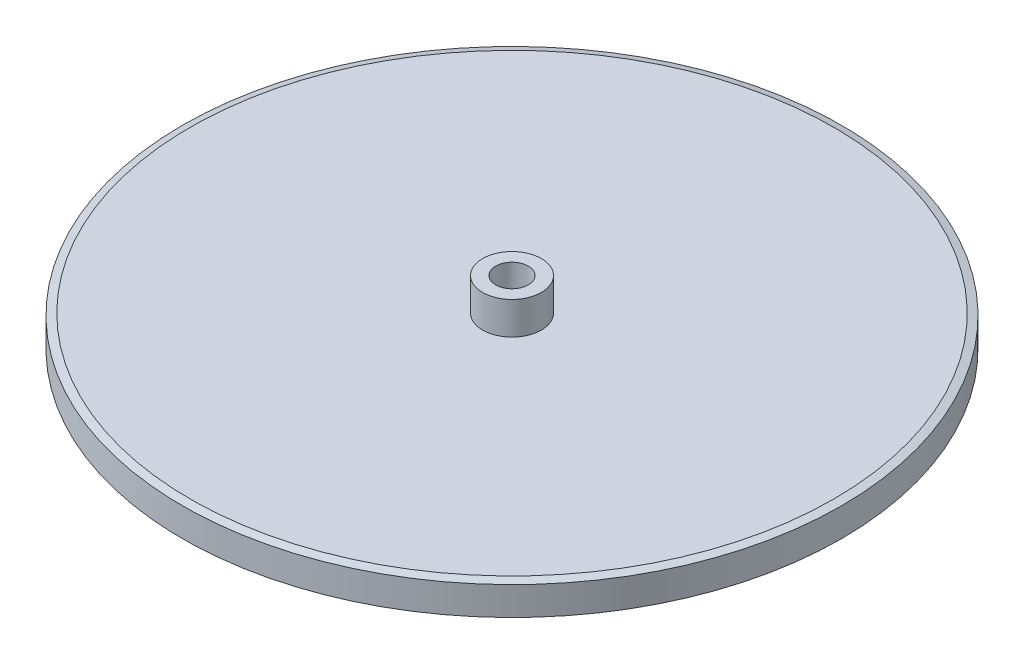
SolidWorks part; units mm, degrees
material "Сталь ШХ15 ГОСТ 801-78"
ref_plane "Plane1" through (0, 0, 0) normal (0, 0, 1) x (1, 0, 0)
ref_plane "Plane2" through (0, 0, 0) normal (0, 1, 0) x (1, 0, 0)
ref_plane "Plane3" through (0, 0, 0) normal (1, 0, 0) x (0, 0, -1)
sketch "Эскиз1" plane through (0, 0, 0) normal (0, 0, 1) x (1, 0, 0)
  line L0 (0, 0) -> (50.5, 0)
  line L1 (50.5, 0) -> (50.5, 5)
  line L2 (50.5, 5) -> (4.5, 5)
  line L3 (4.5, 5) -> (4.5, 10)
  line L4 (4.5, 10) -> (0, 10)
  line L5 (0, 10) -> (0, 0)
  dimension "D1" = 5
  dimension "30" = 50.5
  dimension "D3" = 4.5
  dimension "D4" = 5
ref_axis "Ось1" through (0, 10, 0) along (0, -1, 0)
revolve "Повернуть2" add sketch "Эскиз1" angle 360 about axis through (0, 10, 0) along (0, -1, 0)
chamfer "Фаска1" distance 1.175 angle 15 1 edges at (-50.5, 5, 0) first distance on face at (-4.5, 5, 0)
chamfer "Фаска2" distance 1.175 angle 15 1 edges at (-50.5, 0, 0) first distance on face at (-50.5, 0, 0)
sketch "Эскиз2" plane through (0, 0, 0) normal (0, -1, 0) x (-1, 0, 0)
  circle A0 centre (0, 0) radius 2.5
sketch "Эскиз3" plane through (0, 0, 0) normal (0, 0, 1) x (1, 0, 0)
  circle A0 centre (0, 7.5683) radius 1
extrude "Вырез-Вытянуть3" cut sketch "Эскиз2" against normal through all both contours A0
